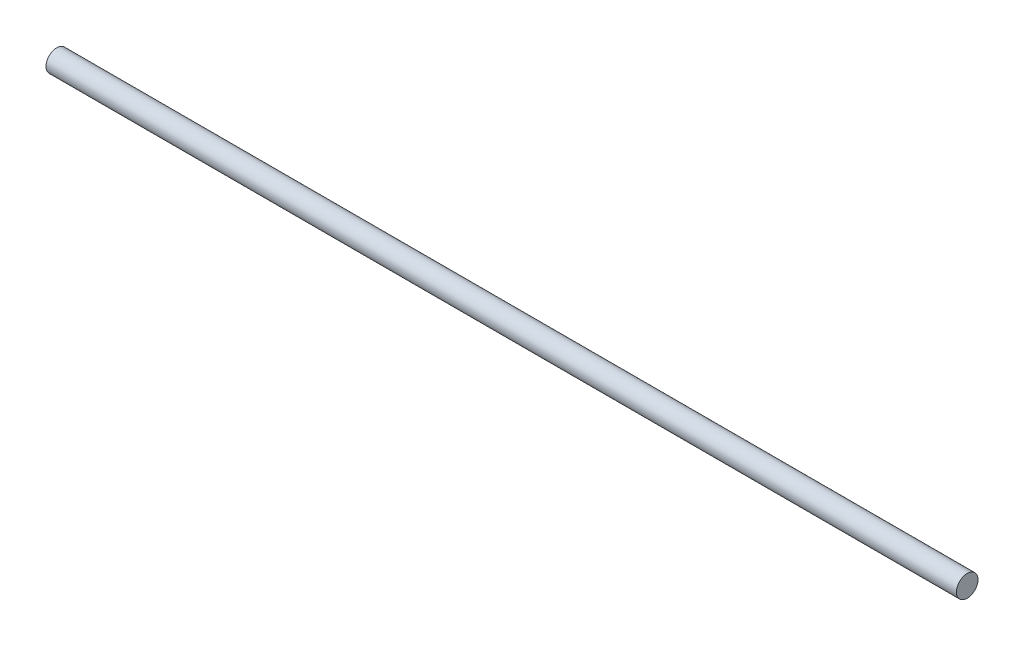
SolidWorks part; units mm, degrees
material "6061-T4 (SS)"
ref_plane "Front Plane" through (0, 0, 0) normal (0, 0, 1) x (1, 0, 0)
ref_plane "Top Plane" through (0, 0, 0) normal (0, 1, 0) x (1, 0, 0)
ref_plane "Right Plane" through (0, 0, 0) normal (1, 0, 0) x (0, 0, -1)
sketch "Sketch1" plane through (0, 0, 0) normal (1, 0, 0) x (0, 0, -1)
  circle A0 centre (0, 0) radius 12.5
  dimension "D1" = 25
extrude "Boss-Extrude1" add sketch "Sketch1" along normal blind 527.5 and the other way blind 527.5
sketch "Sketch2" plane through (0, 0, 0) normal (0, 0, 1) x (1, 0, 0)
  line L0 (0, 0) -> (-527.5, 0)
  line L1 (-527.5, 12.5) -> (-527.5, -12.5) construction
  circle A0 centre (-527.5, 0) radius 44
  circle A1 centre (-527.5, 0) radius 100
  circle A2 centre (-483.5, 0) radius 0.1
  point P9 (-427.5, 0)
  point P10 (-483.5, 0)
  dimension "D1" = 88
  dimension "D2" = 200
